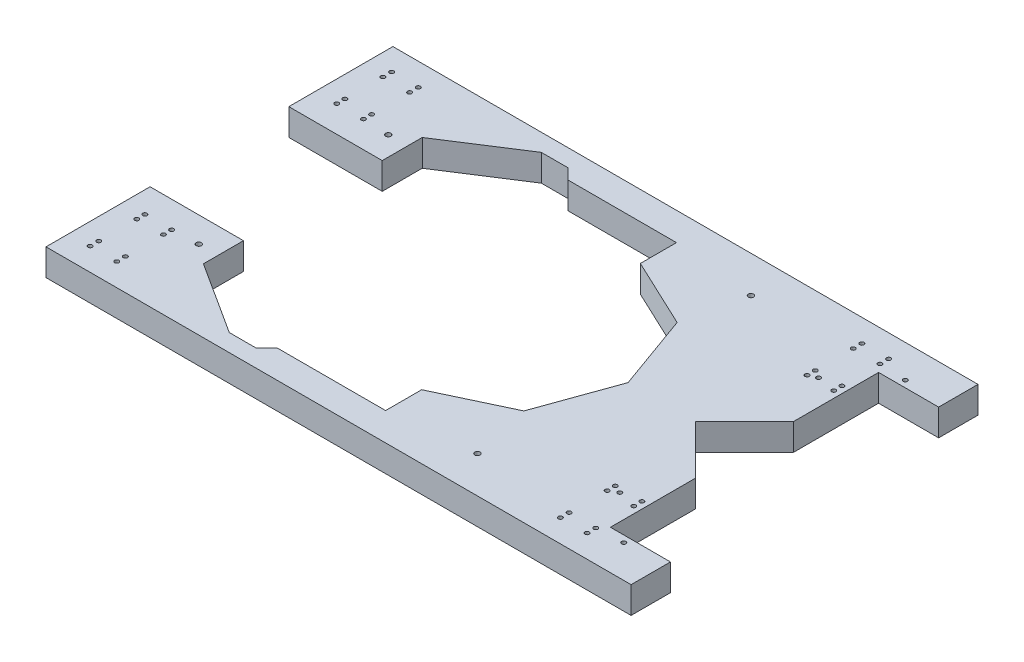
SolidWorks part; units mm, degrees
note: '?' marks a value the reader was unsure of.
material "Magnesium Alloy"
ref_plane "Front Plane" through (0, 0, 0) normal (0, 0, 1) x (1, 0, 0)
ref_plane "Top Plane" through (0, 0, 0) normal (0, 1, 0) x (1, 0, 0)
ref_plane "Right Plane" through (0, 0, 0) normal (1, 0, 0) x (0, 0, -1)
sketch "Sketch1" plane through (0, 0, 0) normal (0, 1, 0) x (1, 0, 0)
  line L0 (0, 471.9498) -> (0, -504.9384) construction
  line L1 (-300.0375, 165.1) -> (300.0375, 165.1)
  line L2 (-300.0375, 165.1) -> (-300.0375, -165.1)
  line L3 (-300.0375, -165.1) -> (300.0375, -165.1)
  line L4 (300.0375, 165.1) -> (300.0375, -165.1)
  line L5 (-636.3607, 0) -> (748.0963, 0) construction
  dimension "D1" = 600.075
  dimension "D2" = 330.2
extrude "Boss-Extrude1" add sketch "Sketch1" along normal blind 25.4
sketch "Sketch2" plane through (-300.0375, 0, 0) normal (-1, 0, 0) x (0, 0, 1)
  line L0 (-165.1, 12.7) -> (165.1, 12.7) construction
  line L1 (-165.1, 25.4) -> (-165.1, 0) construction
  line L2 (165.1, 25.4) -> (165.1, 0) construction
  text T0 "Back" font "Century Gothic" height 19.05
extrude "Cut-Extrude1" cut sketch "Sketch2" against normal blind 2.54
sketch "Sketch3" plane through (300.0375, 0, 0) normal (1, 0, 0) x (0, 0, -1)
  line L0 (-165.1, 12.7) -> (165.1, 12.7) construction
  line L1 (-165.1, 25.4) -> (-165.1, 0) construction
  line L2 (165.1, 25.4) -> (165.1, 0) construction
  text T0 "Front" font "Century Gothic" height 19.05
extrude "Cut-Extrude2" cut sketch "Sketch3" against normal blind 2.54
sketch "Sketch4" plane through (0, 0, 0) normal (0, -1, 0) x (1, 0, 0)
  line L0 (407.1831, 0) -> (-551.8052, 0) construction
  line L1 (-113.3475, 138.43) -> (39.6875, 138.43)
  line L2 (-113.3475, 138.43) -> (-113.3475, -138.43)
  line L3 (-113.3475, -138.43) -> (39.6875, -138.43)
  line L4 (39.6875, 138.43) -> (39.6875, -138.43)
  line L5 (55, 0) -> (-55, 0) construction
  line L6 (-300.0375, -165.1) -> (-300.0375, 165.1) construction
  line L7 (300.0375, 165.1) -> (300.0375, -165.1) construction
  line L10 (-300.0375, 165.1) -> (300.0375, 165.1) construction
  dimension "D1" = 186.69
  dimension "D2" = 260.35
  dimension "D3" = 26.67
extrude "Cut-Extrude3" cut sketch "Sketch4" against normal up to next
ref_plane "Plane1" through (223.8375, 0, 0) normal (1, 0, 0) x (0, 0, -1)
ref_plane "Plane2" through (-223.8375, 0, 0) normal (-1, 0, 0) x (0, 0, 1)
sketch "Sketch7" plane through (0, 25.4, 0) normal (0, 1, 0) x (1, 0, 0)
  line L0 (-300.0375, -29.6562) -> (-300.0375, -165.1) construction
  line L1 (-300.0375, -165.1) -> (300.0375, -165.1) construction
  point P0 (-236.5375, -91.2978)
  point P1 (-236.5375, -135.2474)
  point P2 (-211.1375, -135.2474)
  point P3 (-211.1375, -91.2978)
  dimension "D1" = 63.5
  dimension "D2" = 63.5
  dimension "D3" = 88.9
  dimension "D4" = 88.9
  dimension "D5" = 29.8526
  dimension "D6" = 29.8526
  dimension "D7" = 43.9496
  dimension "D8" = 43.9496
hole_wizard "#21 (0.159) Diameter Hole1" positions "Sketch10" profile "Sketch11" hole size "#21" standard "ANSI Inch" end condition through all
sketch "Sketch10" plane through (0, 25.4, 0) normal (0, 1, 0) x (1, 0, 0)
  point P0 (-236.5375, -91.2978)
  point P3 (-211.1375, -91.2978)
  point P6 (-211.1375, -135.2474)
  point P9 (-236.5375, -135.2474)
sketch "Sketch11" plane through (-236.5375, 25.4, 91.2978) normal (1, 0, 0) x (0, 0, 1)
  line L0 (0, 0) -> (0, 25.4)
  line L1 (0, 25.4) -> (2.0193, 25.4)
  line L2 (2.0193, 25.4) -> (2.0193, 0)
  line L5 (2.0193, 0) -> (0, 0)
  line L11 (0, -6.35) -> (0, 107.95) construction
  dimension "Thru Hole Dia." = 4.0386
  dimension "Thru Hole Depth" = 25.4
mirror "Mirror3" about plane through (0, 0, 0) normal (1, 0, 0) of "#21 (0.159) Diameter Hole1"
mirror "Mirror4" about plane through (0, 0, 0) normal (0, 0, 1) of "Mirror3", "#21 (0.159) Diameter Hole1"
ref_axis "Axis1" through (-236.5375, 0, 91.2978) along (0, 1, 0)?
ref_axis "Axis2" through (-211.1375, 0, 91.2978) along (0, 1, 0)?
ref_axis "Axis3" through (-211.1375, 0, 135.2474) along (0, 1, 0)?
ref_axis "Axis4" through (-236.5375, 0, 135.2474) along (0, 1, 0)?
sketch "Sketch12" plane through (0, 25.4, 0) normal (0, 1, 0) x (1, 0, 0)
  point P0 (78.8458, -130.175)
ref_plane "Plane3" through (0, 0, 130.175) normal (0, 0, 1) x (1, 0, 0)
sketch "Sketch13" plane through (0, 0, 130.175) normal (0, 0, 1) x (1, 0, 0)
  line L0 (78.8458, 65.775) -> (78.8458, -43.461) construction
hole_wizard "Ø5.0mm Dowel Hole2" positions "Sketch16" profile "Sketch17" hole size "Ø5.0" standard "ANSI Metric" end condition through all
sketch "Sketch16" plane through (0, 25.4, 0) normal (0, 1, 0) x (1, 0, 0)
  circle A0 centre (118.8508, -130.175) radius 2.54
  circle A1 centre (118.8508, 130.175) radius 2.54
  circle A2 centre (-186.3725, 90.17) radius 2.54
  circle A3 centre (-186.3725, -90.17) radius 2.54
  point P3 (118.8508, -130.175)
  point P9 (118.8508, 130.175)
  point P12 (-186.3725, 90.17)
  point P21 (-186.3725, -90.17)
  point P24 (118.8508, -130.175)
sketch "Sketch17" plane through (118.8508, 25.4, 130.175) normal (1, 0, 0) x (0, 0, 1)
  line L0 (0, 0) -> (0, 25.4)
  line L1 (0, 25.4) -> (2.5, 25.4)
  line L2 (2.5, 25.4) -> (2.5, 0)
  line L5 (2.5, 0) -> (0, 0)
  line L11 (0, -6.35) -> (0, 107.95) construction
  dimension "Thru Hole Dia." = 5
  dimension "Thru Hole Depth" = 25.4
sketch "Sketch18" plane through (0, 25.4, 0) normal (0, 1, 0) x (1, 0, 0)
  line L0 (300.0375, 30.4067) -> (300.0375, 165.1) construction
  line L1 (300.0375, 127.635) -> (242.8875, 127.635)
  line L2 (300.0375, 127.635) -> (300.0375, -127.635)
  line L3 (300.0375, -127.635) -> (242.8875, -127.635)
  line L4 (242.8875, 127.635) -> (242.8875, -127.635)
  line L5 (300.0375, 165.1) -> (-300.0375, 165.1) construction
  line L6 (-300.0375, -165.1) -> (300.0375, -165.1) construction
  dimension "D1" = 37.465
  dimension "D2" = 37.465
  dimension "D3" = 57.15
extrude "Cut-Extrude4" cut sketch "Sketch18" against normal up to next
sketch "Sketch19" plane through (0, 12.7, 0) normal (0, -1, 0) x (-1, 0, 0)
  circle A0 centre (-218.7586, 94.615) radius 2.032
  circle A1 centre (-218.7586, 94.615) radius 2.032 construction
  circle A2 centre (-218.7586, -94.615) radius 2.032
  circle A3 centre (-218.7586, -94.615) radius 2.032 construction
  circle A4 centre (-176.2125, 133.985) radius 2.032
  circle A5 centre (-176.2125, 133.985) radius 2.032 construction
  circle A6 centre (-176.2125, -133.985) radius 2.032
  circle A7 centre (-176.2125, -133.985) radius 2.032 construction
extrude "Cut-Extrude5" cut sketch "Sketch19" along normal blind 12.7
ref_axis "Axis5" through (176.2125, 0, -133.985) along (0, 1, 0)?
ref_axis "Axis6" through (176.2125, 0, 133.985) along (0, 1, 0)?
ref_axis "Axis7" through (218.7586, 0, -94.615) along (0, 1, 0)?
ref_axis "Axis8" through (218.7586, 0, 94.615) along (0, 1, 0)?
sketch "Sketch20" plane through (0, 25.4, 0) normal (0, 1, 0) x (1, 0, 0)
  line L0 (300.0375, 165.1) -> (-300.0375, 165.1) construction
  line L1 (300.0375, 127.635) -> (300.0375, 165.1) construction
  circle A0 centre (236.5375, 143.51) radius 2.0193
  dimension "D1" = 21.59
  dimension "D2" = 63.5
extrude "Cut-Extrude6" cut sketch "Sketch20" against normal up to next
sketch "Sketch21" plane through (0, 25.4, 0) normal (0, 1, 0) x (1, 0, 0)
  line L0 (300.0375, 165.1) -> (-300.0375, 165.1) construction
  line L1 (300.0375, 127.635) -> (300.0375, 165.1) construction
  circle A0 centre (211.1375, 143.51) radius 2.0193
  circle A1 centre (211.1375, 99.06) radius 2.0193
  circle A2 centre (236.5375, 99.06) radius 2.0193
  circle A3 centre (236.5375, 143.51) radius 2.0193 construction
  dimension "D1" = 21.59
  dimension "D2" = 25.4
  dimension "D3" = 4.0386
  dimension "D4" = 44.45
  dimension "D5" = 44.45
  dimension "D6" = 63.5
  dimension "D7" = 4.0386
  dimension "D8" = 25.4
  dimension "D9" = 4.0386
extrude "Cut-Extrude7" cut sketch "Sketch21" against normal up to next
pattern_linear "LPattern1" count 2 spacing 447.675 along (-1, 0, 0) of "Cut-Extrude7", "Cut-Extrude6"
mirror "Mirror5" about plane through (0, 0, 0) normal (0, 0, 1) of "LPattern1", "Cut-Extrude6", "Cut-Extrude7"
sketch "Sketch22" plane through (0, 25.4, 0) normal (0, 1, 0) x (1, 0, 0)
  line L0 (300.0375, -165.1) -> (300.0375, -127.635) construction
  line L1 (160.3375, -127.635) -> (300.0375, -127.635) construction
  circle A0 centre (261.9375, -133.985) radius 2.032
  dimension "D1" = 4.064
  dimension "D2" = 38.1
  dimension "D3" = 6.35
extrude "Cut-Extrude8" cut sketch "Sketch22" against normal up to next
mirror "Mirror6" about plane through (0, 0, 0) normal (0, 0, 1) of "Cut-Extrude8"
sketch "Sketch23" plane through (0, 25.4, 0) normal (0, 1, 0) x (1, 0, 0)
  circle A0 centre (-236.5375, 143.51) radius 2.0193
  circle A1 centre (-236.5375, 143.51) radius 3.6068
  circle A2 centre (-211.1375, 143.51) radius 2.0193
  circle A3 centre (-211.1375, 143.51) radius 3.6068
  circle A4 centre (-236.5375, 135.2474) radius 2.0193
  circle A5 centre (-236.5375, 135.2474) radius 3.6068
  circle A6 centre (-211.1375, 135.2474) radius 2.0193
  circle A7 centre (-211.1375, 135.2474) radius 3.6068
  circle A8 centre (-236.5375, 99.06) radius 2.0193
  circle A9 centre (-236.5375, 99.06) radius 3.6068
  circle A10 centre (-236.5375, 91.2978) radius 2.0193
  circle A11 centre (-236.5375, 91.2978) radius 3.6068
  circle A12 centre (-211.1375, 99.06) radius 2.0193
  circle A13 centre (-211.1375, 99.06) radius 3.6068
  circle A14 centre (-211.1375, 91.2978) radius 2.0193
  circle A15 centre (-211.1375, 91.2978) radius 3.6068
  circle A16 centre (-186.3725, 90.17) radius 2.5006
  circle A17 centre (-186.3725, 90.17) radius 4.0881
  circle A18 centre (118.8508, 130.175) radius 2.5006
  circle A19 centre (118.8508, 130.175) radius 4.0881
  circle A20 centre (176.2125, 133.985) radius 2.032
  circle A21 centre (211.1375, 99.06) radius 2.0193
  circle A22 centre (211.1375, 91.2978) radius 2.0193
  circle A23 centre (218.7586, 94.615) radius 2.032
  circle A24 centre (211.1375, 135.2474) radius 2.0193
  circle A25 centre (211.1375, 143.51) radius 2.0193
  circle A26 centre (236.5375, 143.51) radius 2.0193
  circle A27 centre (236.5375, 135.2474) radius 2.0193
  circle A28 centre (236.5375, 99.06) radius 2.0193
  circle A29 centre (236.5375, 91.2978) radius 2.0193
  circle A30 centre (261.9375, 133.985) radius 2.032
  circle A31 centre (176.2125, 133.985) radius 3.6195
  circle A32 centre (211.1375, 143.51) radius 3.6068
  circle A33 centre (211.1375, 135.2474) radius 3.6068
  circle A34 centre (211.1375, 99.06) radius 3.6068
  circle A35 centre (211.1375, 91.2978) radius 3.6068
  circle A36 centre (218.7586, 94.615) radius 3.6195
  circle A37 centre (236.5375, 91.2978) radius 3.6068
  circle A38 centre (236.5375, 99.06) radius 3.6068
  circle A39 centre (236.5375, 135.2474) radius 3.6068
  circle A40 centre (236.5375, 143.51) radius 3.6068
  circle A41 centre (261.9375, 133.985) radius 3.6195
  dimension "D1" = 1.5875
  dimension "D2" = 1.5875
  dimension "D3" = 1.5875
  dimension "D4" = 1.5875
  dimension "D5" = 1.5875
  dimension "D6" = 1.5875
  dimension "D7" = 1.5875
  dimension "D8" = 1.5875
  dimension "D9" = 1.5875
  dimension "D10" = 4.0386
  dimension "D11" = 4.0386
  dimension "D12" = 4.0386
  dimension "D13" = 4.0386
  dimension "D14" = 5.0013
  dimension "D15" = 4.0386
  dimension "D16" = 4.0386
  dimension "D17" = 4.0386
  dimension "D18" = 4.0386
  dimension "D19" = 1.5875
  dimension "D20" = 4.064
  dimension "D21" = 1.5875
  dimension "D22" = 1.5875
  dimension "D23" = 1.5875
  dimension "D24" = 1.5875
  dimension "D25" = 1.5875
  dimension "D26" = 1.5875
  dimension "D27" = 1.5875
  dimension "D28" = 1.5875
  dimension "D29" = 1.5875
  dimension "D30" = 1.5875
  dimension "D31" = 1.5875
  dimension "D32" = 5.0013
  dimension "D33" = 4.0386
  dimension "D34" = 4.0386
  dimension "D35" = 4.064
  dimension "D36" = 4.0386
  dimension "D37" = 4.0386
  dimension "D38" = 4.0386
  dimension "D39" = 4.0386
  dimension "D40" = 4.0386
  dimension "D41" = 4.0386
  dimension "D42" = 4.064
extrude "Boss-Extrude2" add sketch "Sketch23" against normal up to surface (25.4 mm away) up to face at (261.9375, 0, -131.953)
mirror "Mirror10" about plane through (0, 0, 0) normal (0, 0, 1) of "Boss-Extrude2"
sketch "Sketch24" plane through (0, 25.4, 0) normal (0, 1, 0) x (1, 0, 0)
  line L0 (-256.8857, 165.1) -> (-256.8857, 66.04)
  line L1 (300.0375, 165.1) -> (-300.0375, 165.1) construction
  line L2 (-256.8857, 66.04) -> (-167.9857, 66.04)
  line L3 (-167.9857, 66.04) -> (-167.9857, 104.14)
  line L4 (-167.9857, 104.14) -> (-99.0596, 148.5171)
  line L5 (-99.0596, 148.5171) -> (-73.6596, 148.5171)
  line L6 (-73.6596, 148.5171) -> (-63.5415, 138.43)
  line L7 (-113.3475, 138.43) -> (39.6875, 138.43) construction
  line L8 (-63.5415, 138.43) -> (39.6875, 138.43)
  line L9 (39.6875, 138.43) -> (39.6875, 104.0777)
  line L10 (39.6875, 138.43) -> (39.6875, -138.43) construction
  line L11 (39.6875, 104.0777) -> (105.8305, 72.9194)
  line L12 (105.8305, 72.9194) -> (132.0485, 0)
  line L13 (176.645, 0) -> (-283.1774, 0) construction
  line L14 (105.8305, -72.9194) -> (132.0485, 0)
  line L15 (39.6875, -104.0777) -> (105.8305, -72.9194)
  line L16 (39.6875, -138.43) -> (39.6875, -104.0777)
  line L17 (-63.5415, -138.43) -> (39.6875, -138.43)
  line L18 (-73.6596, -148.5171) -> (-63.5415, -138.43)
  line L19 (-99.0596, -148.5171) -> (-73.6596, -148.5171)
  line L20 (-167.9857, -104.14) -> (-99.0596, -148.5171)
  line L21 (-167.9857, -66.04) -> (-167.9857, -104.14)
  line L22 (-256.8857, -66.04) -> (-167.9857, -66.04)
  line L23 (-256.8857, -165.1) -> (-256.8857, -66.04)
  line L24 (-256.8857, 165.1) -> (-300.0375, 165.1)
  line L25 (-300.0375, 165.1) -> (-300.0375, -165.1)
  line L26 (-300.0375, -165.1) -> (-256.8857, -165.1)
  line L27 (242.8875, 46.4819) -> (196.4056, 0)
  line L28 (242.8875, 127.635) -> (242.8875, -127.635) construction
  line L29 (242.8875, -46.4819) -> (196.4056, 0)
  line L30 (242.8875, 46.4819) -> (242.8875, -46.4819)
  dimension "D1" = 88.9
  dimension "D2" = 99.06
  dimension "D3" = 38.1
  dimension "D4" = 25.4
extrude "Cut-Extrude9" cut sketch "Sketch24" against normal up to next
sketch "Sketch25" plane through (0, 25.4, 0) normal (0, 1, 0) x (1, 0, 0)
  line L0 (242.8875, -46.4819) -> (242.8875, -127.635) construction
  line L1 (-256.8857, -165.1) -> (300.0375, -165.1) construction
  line L2 (374.5788, 0) -> (-346.3995, 0) construction
  circle A0 centre (218.7586, -94.615) radius 2.032
  circle A1 centre (218.7586, 94.615) radius 2.032
  dimension "D1" = 24.1289
  dimension "D2" = 70.485
  dimension "D3" = 4.064
extrude "Cut-Extrude10" cut sketch "Sketch25" against normal up to next
